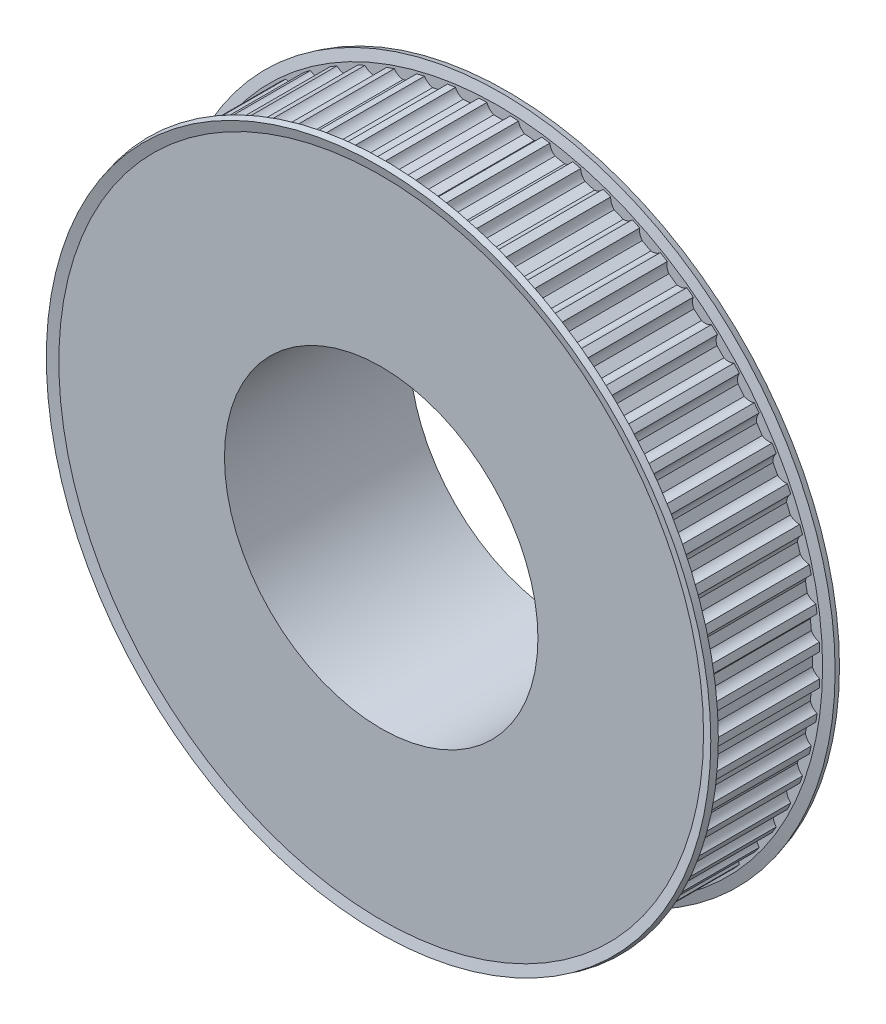
SolidWorks part; units mm, degrees
ref_plane "Front Plane" through (0, 0, 0) normal (0, 0, 1) x (1, 0, 0)
ref_plane "Top Plane" through (0, 0, 0) normal (0, 1, 0) x (1, 0, 0)
ref_plane "Right Plane" through (0, 0, 0) normal (1, 0, 0) x (0, 0, -1)
sketch "Sketch1" plane through (0, 0, 0) normal (1, 0, 0) x (0, 0, -1)
  line L0 (-181.2808, 0) -> (196.2562, 0) construction
  line L1 (0, 38.1) -> (45, 38.1)
  line L2 (45, 38.1) -> (45, 53.6)
  line L3 (45, 53.6) -> (30, 53.6)
  line L4 (30, 53.6) -> (30, 78.1)
  line L5 (30, 78.1) -> (0, 78.1)
  line L6 (0, 78.1) -> (0, 38.1)
  dimension "D1" = 38.1
  dimension "D2" = 40
  dimension "D3" = 30
  dimension "D4" = 15
  dimension "D5" = 15.5
revolve "Revolve1" add sketch "Sketch1" angle 360 about L0
sketch "Sketch2" plane through (0, 0, 0) normal (0, 0, 1) x (1, 0, 0)
  line L0 (-1.199, 76.25) -> (1.199, 76.25)
  line L1 (3.6742, 79) -> (3.75, 79)
  line L2 (-3.75, 81) -> (3.75, 81)
  line L3 (-3.75, 81) -> (-3.75, 79)
  line L4 (-3.75, 79) -> (-3.6742, 79)
  line L5 (3.75, 81) -> (3.75, 79)
  line L6 (0, 79) -> (0, 77.2528) construction
  arc A0 (-2.9394, 78.4) -> (-1.199, 76.25) centre (0, 79) ccw
  arc A1 (1.199, 76.25) -> (2.9394, 78.4) centre (0, 79) ccw
  arc A2 (2.9394, 78.4) -> (3.6742, 79) centre (3.6742, 78.25) cw
  arc A3 (-2.9394, 78.4) -> (-3.6742, 79) centre (-3.6742, 78.25) ccw
  point P13 (3, 79)
  point P16 (-3, 79)
  dimension "D1" = 3
  dimension "D6" = 0.75
  dimension "D2" = 7.5
  dimension "D3" = 2
  dimension "D4" = 2.75
  dimension "D5" = 79
extrude "Cut-Extrude1" cut sketch "Sketch2" against normal through all
pattern_circular "CirPattern1" count 64 over 360 about axis through (0, 0, 181.2808) along (0, 0, 1) of "Cut-Extrude1"
sketch "Sketch3" plane through (0, 0, 0) normal (1, 0, 0) x (0, 0, -1)
  line L0 (1.4489, 78.7482) -> (0, 78.3599)
  line L1 (0, 78.7482) -> (1.4489, 78.7482) construction
  line L2 (0, 78.7482) -> (0, 73.7482)
  line L3 (0, 73.7482) -> (1.4489, 73.7482)
  line L4 (1.4489, 78.7482) -> (1.4489, 73.7482)
  line L5 (1.4489, 78.7482) -> (0.8058, 81.1482)
  line L6 (0, 78.3599) -> (-0.6431, 80.7599)
  line L7 (0.8058, 81.1482) -> (-0.6431, 80.7599)
  line L10 (15, 75.5133) -> (15, 69.0594) construction
  line L12 (30, 73.7482) -> (28.5511, 73.7482)
  line L13 (30, 78.7482) -> (30, 73.7482)
  line L14 (28.5511, 78.7482) -> (28.5511, 73.7482)
  line L15 (28.5511, 78.7482) -> (29.1942, 81.1482)
  line L16 (29.1942, 81.1482) -> (30.6431, 80.7599)
  line L17 (30, 78.3599) -> (30.6431, 80.7599)
  line L18 (-34.4133, 0) -> (76.7407, 0) construction
  line L19 (0, 77.1035) -> (0, 75.0188) construction
  line L20 (30, 78.0482) -> (0, 78.0482) construction
  line L21 (0, 75.5133) -> (30, 75.5133) construction
  dimension "D1" = 165
  dimension "D2" = 1.5
  dimension "D3" = 2.4
  dimension "D4" = 0.7
  dimension "D5" = 5
revolve "Revolve2" add sketch "Sketch3" angle 360 about L18 region at (0, 76.1524, -0.7342) region at (0, 79.7541, -0.4029) region at (0, 77.4081, -29.3813)
